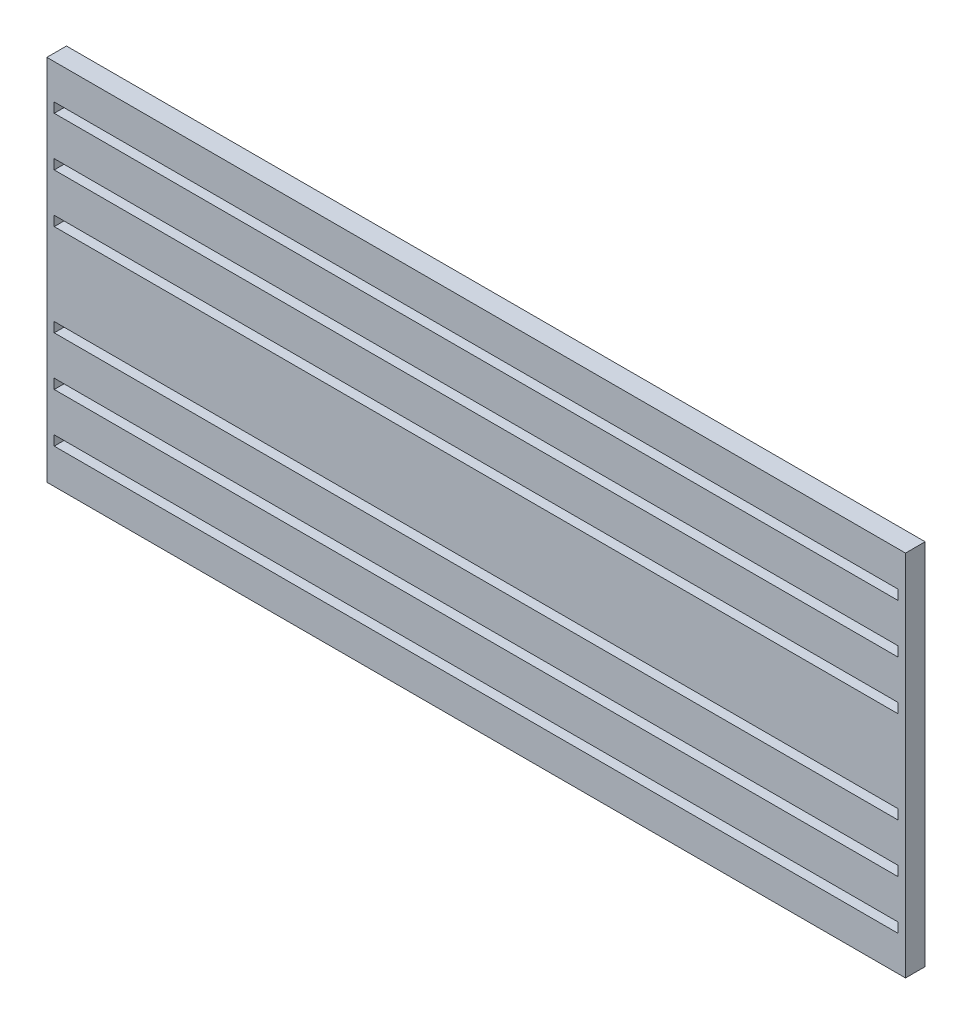
SolidWorks part; units mm, degrees
ref_plane "Front Plane" through (0, 0, 0) normal (0, 0, 1) x (1, 0, 0)
ref_plane "Top Plane" through (0, 0, 0) normal (0, 1, 0) x (1, 0, 0)
ref_plane "Right Plane" through (0, 0, 0) normal (1, 0, 0) x (0, 0, -1)
sketch "Sketch1" plane through (0, 0, 0) normal (0, 0, 1) x (1, 0, 0)
  line L1 (111.125, -47.625) -> (-111.125, -47.625)
  line L2 (111.125, -47.625) -> (111.125, 47.625)
  line L3 (111.125, 47.625) -> (-111.125, 47.625)
  line L4 (-111.125, -47.625) -> (-111.125, 47.625)
  line L5 (111.125, -47.625) -> (-111.125, 47.625) construction
  line L6 (111.125, 47.625) -> (-111.125, -47.625) construction
  point P0 (0, 0)
  dimension "D1" = 95.25
  dimension "D2" = 222.25
extrude "Boss-Extrude1" add sketch "Sketch1" along normal blind 5.08
sketch "Sketch2" plane through (0, 0, 0) normal (0, 0, -1) x (-1, 0, 0)
  line L0 (0, 47.625) -> (0, -47.625) construction
  line L1 (-111.125, 47.625) -> (111.125, 47.625) construction
  line L2 (111.125, -47.625) -> (-111.125, -47.625) construction
  line L3 (111.125, 0) -> (-111.125, 0) construction
  line L4 (111.125, 47.625) -> (111.125, -47.625) construction
  line L5 (-111.125, -47.625) -> (-111.125, 47.625) construction
  line L6 (0, 0) -> (0, 47.625) construction
  line L7 (0, 0) -> (0, -47.625) construction
  line L8 (0, -23.8125) -> (0, -47.625) construction
  line L9 (0, -23.8125) -> (0, 0) construction
  line L10 (0, -23.8125) -> (0, -47.625) construction
  line L11 (0, 0) -> (0, 47.625) construction
  line L12 (0, 23.8125) -> (0, 47.625) construction
  line L13 (0, 23.8125) -> (0, 0) construction
  line L14 (0, 0) -> (0, 23.8125) construction
  line L15 (-109.22, 25.8763) -> (109.22, 25.8763)
  line L16 (-109.22, 13.1763) -> (109.22, 13.1763)
  line L17 (-109.22, 13.1763) -> (-109.22, 10.6363)
  line L18 (-109.22, 10.6363) -> (109.22, 10.6363)
  line L19 (109.22, 13.1763) -> (109.22, 10.6363)
  line L20 (-109.22, 13.1763) -> (109.22, 10.6363) construction
  line L21 (-109.22, 10.6363) -> (109.22, 13.1763) construction
  line L22 (-109.22, 23.3363) -> (109.22, 23.3363)
  line L23 (-109.22, 25.8763) -> (-109.22, 23.3363)
  line L24 (109.22, 25.8763) -> (109.22, 23.3363)
  line L25 (-109.22, 38.5763) -> (109.22, 38.5763)
  line L26 (-109.22, 36.0363) -> (109.22, 36.0363)
  line L27 (-109.22, 38.5763) -> (-109.22, 36.0363)
  line L28 (109.22, 38.5763) -> (109.22, 36.0363)
  line L29 (109.22, -13.1763) -> (109.22, -10.6363)
  line L30 (-109.22, -10.6362) -> (109.22, -10.6363)
  line L31 (-109.22, -13.1762) -> (109.22, -13.1763)
  line L32 (-109.22, -13.1762) -> (-109.22, -10.6362)
  line L33 (-109.22, -25.8762) -> (-109.22, -23.3362)
  line L34 (-109.22, -23.3362) -> (109.22, -23.3363)
  line L35 (-109.22, -25.8762) -> (109.22, -25.8763)
  line L36 (109.22, -25.8763) -> (109.22, -23.3363)
  line L37 (109.22, -38.5763) -> (109.22, -36.0363)
  line L38 (-109.22, -38.5762) -> (-109.22, -36.0362)
  line L39 (-109.22, -38.5762) -> (109.22, -38.5763)
  line L40 (-109.22, -36.0362) -> (109.22, -36.0363)
  point P16 (0, 11.9063)
  dimension "D1" = 2.54
  dimension "D2" = 218.44
  dimension "D3" = 3
extrude "Cut-Extrude1" cut sketch "Sketch2" against normal blind 5.08
